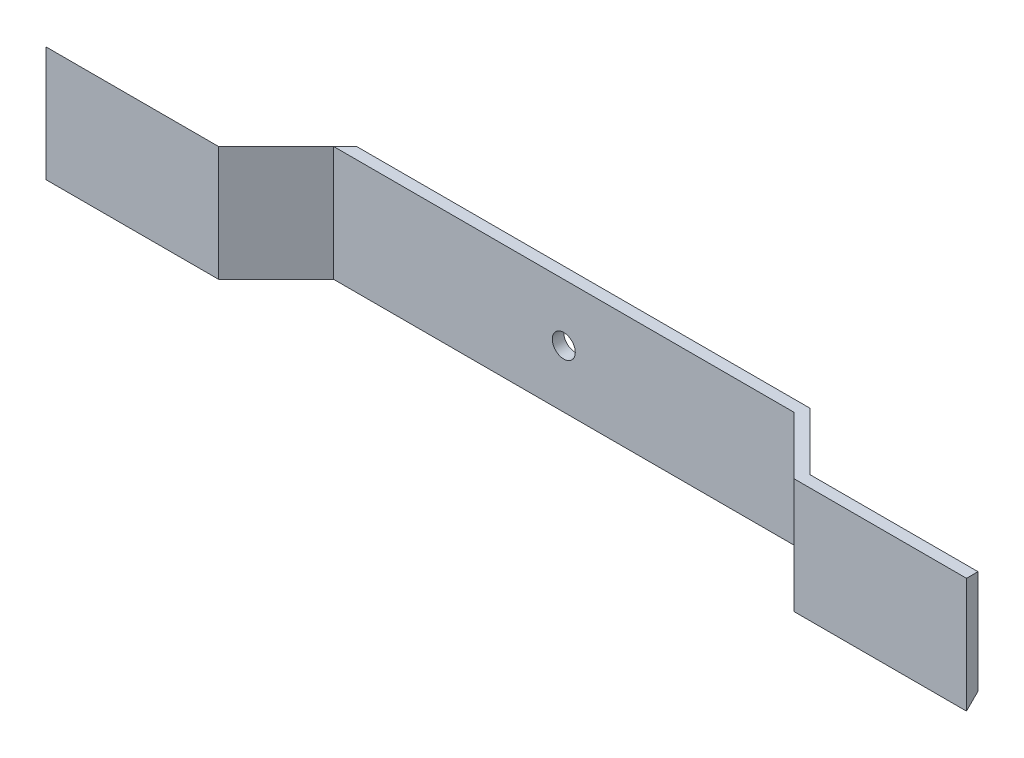
SolidWorks part; units mm, degrees
ref_plane "Front Plane" through (0, 0, 0) normal (0, 0, 1) x (1, 0, 0)
ref_plane "Top Plane" through (0, 0, 0) normal (0, 1, 0) x (1, 0, 0)
ref_plane "Right Plane" through (0, 0, 0) normal (1, 0, 0) x (0, 0, -1)
sketch "Sketch2" plane through (0, 0, 0) normal (0, 1, 0) x (1, 0, 0)
  line L0 (-27.2373, 0) -> (12.7627, 0)
  line L1 (-27.2373, 0) -> (-32.2373, -5)
  line L2 (12.7627, 0) -> (17.7627, -5)
  line L3 (-32.2373, -5) -> (-47.2373, -5)
  line L4 (17.7627, -5) -> (32.7627, -5)
  line L5 (18.1769, -4) -> (32.7627, -4)
  line L6 (13.1769, 1) -> (18.1769, -4)
  line L7 (-27.6515, 1) -> (13.1769, 1)
  line L8 (-27.6515, 1) -> (-32.6515, -4)
  line L9 (-32.6515, -4) -> (-47.2373, -4)
  line L10 (-47.2373, -4) -> (-47.2373, -5)
  line L11 (32.7627, -4) -> (32.7627, -5)
  dimension "D1" = 135
  dimension "D2" = 40
  dimension "D3" = 5
  dimension "D4" = 5
  dimension "D5" = 15
  dimension "D6" = 15
  dimension "D7" = 1
extrude "Bottom Blade Extrude" add sketch "Sketch2" along normal blind 10
chamfer "Bottom Blade Cut 1" distance 1 angle 45 2 edges at (-30.1515, 10, 1.5) (-39.9444, 10, 4)
chamfer "Bottom Blade Cut 2" distance 1 angle 45 2 edges at (15.6769, 0, 1.5) (25.4698, 0, 4)
sketch "Sketch3" plane through (0, 0, 0) normal (0, 0, 1) x (1, 0, 0)
  line L0 (-27.2373, 10) -> (12.7627, 0) construction
  line L1 (12.7627, 10) -> (-27.2373, 0) construction
  circle A0 centre (-7.2373, 5) radius 1
  dimension "D1" = 2
extrude "Hole for Screw ( Bottom Blade)" cut sketch "Sketch3" against normal blind 20
